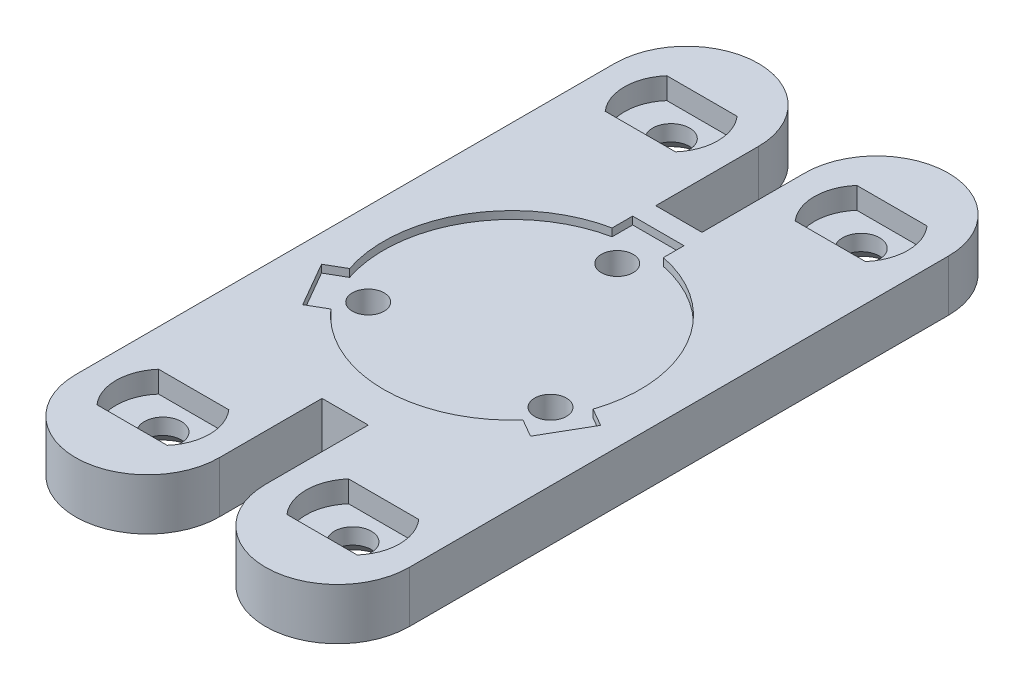
SolidWorks part; units mm, degrees
note: The reader was unsure of these and kept them because the rebuilt part matched: shared geometry of "Sketch6<4>".
ref_plane "Front Plane" through (0, 0, 0) normal (0, 0, 1) x (1, 0, 0)
ref_plane "Top Plane" through (0, 0, 0) normal (0, 1, 0) x (1, 0, 0)
ref_plane "Right Plane" through (0, 0, 0) normal (1, 0, 0) x (0, 0, -1)
sketch "Sketch1" plane through (0, 0, 0) normal (0, 1, 0) x (1, 0, 0)
  line L0 (-16.25, 16.25) -> (-16.25, 26.25)
  line L1 (-16.25, 16.25) -> (16.25, 16.25)
  line L2 (-16.25, 16.25) -> (-16.25, -16.25)
  line L4 (16.25, 16.25) -> (16.25, -16.25)
  line L5 (-16.25, 16.25) -> (16.25, -16.25) construction
  line L6 (-16.25, -16.25) -> (16.25, 16.25) construction
  line L7 (-2.25, 26.25) -> (-2.25, 16.25)
  line L8 (0, 0) -> (0, 7.4679) construction
  line L9 (-16.25, -16.25) -> (16.25, -16.25)
  arc A0 (-16.25, 26.25) -> (-2.25, 26.25) centre (-9.25, 26.25) cw
  point P10 (0, 0)
  dimension "D2" = 14
  dimension "D1" = 32.5
  dimension "D4" = 10
extrude "Boss-Extrude1" add sketch "Sketch1" along normal blind 5
sketch "Sketch2" plane through (0, 0, 0) normal (0, -1, 0) x (1, 0, 0)
  line L11 (-9.25, -16.25) -> (-9.25, -33.25) construction
  line L12 (-16.25, -16.25) -> (-2.25, -16.25) construction
  line L13 (-16.25, 16.25) -> (-16.25, -26.25) construction
  arc A2 (-16.25, -26.25) -> (-2.25, -26.25) centre (-9.25, -26.25) ccw construction
  point P69 (-9.25, -24.75)
hole_wizard "CSK for M3 Flat Head Machine Screw1" positions "Sketch2" profile "Sketch3" countersink size "M3" standard "ANSI Metric" end condition through all
sketch "Sketch3" plane through (-9.25, 0, -24.75) normal (1, 0, 0) x (0, 0, -1)
  line L0 (0, 0) -> (0, 5)
  line L1 (0, 5) -> (1.8, 5)
  line L2 (1.8, 5) -> (1.8, 1.35)
  line L3 (1.8, 1.35) -> (3.15, 0)
  line L5 (3.15, 0) -> (0, 0)
  line L6 (-1.8, 1.35) -> (-3.15, 0) construction
  line L11 (0, -6.35) -> (0, 107.95) construction
  dimension "Thru Hole Dia." = 3.6
  dimension "Thru Hole Depth" = 5
  dimension "Near C'Sink Dia." = 6.3
  dimension "Near C'Sink Angle" = 90
sketch "Sketch16" plane through (0, 5, 0) normal (0, 1, 0) x (1, 0, 0)
  line L0 (-9.25, 24.75) -> (-6.7386, 24.75) construction
  line L1 (-12.6709, 27.75) -> (-5.8291, 27.75)
  line L2 (-12.6709, 21.75) -> (-5.8291, 21.75)
  circle A0 centre (-9.25, 24.75) radius 4.55
  dimension "D1" = 9.1
  dimension "D2" = 6
extrude "Cut-Extrude7" cut sketch "Sketch16" against normal blind 2.1
mirror "Mirror2" about plane through (0, 0, 0) normal (1, 0, 0) of "Boss-Extrude1", "CSK for M3 Flat Head Machine Screw1", "Cut-Extrude7"
mirror "Mirror6" about plane through (0, 0, 0) normal (0, 0, 1) of "Mirror2", "Boss-Extrude1", "CSK for M3 Flat Head Machine Screw1", "Cut-Extrude7"
sketch "Sketch6" plane through (0, 5, 0) normal (0, 1, 0) x (1, 0, 0)
  line L1 (-2.5, 14.25) -> (2.5, 14.25)
  line L2 (0, 0) -> (0, 4.4626) construction
  line L3 (-2.5, 14.25) -> (-2.5, 10.75)
  line L4 (-2.5, 10.75) -> (2.5, 10.75)
  line L5 (2.5, 14.25) -> (2.5, 10.75)
  line L6 (-2.5, 14.25) -> (2.5, 10.75) construction
  line L7 (-2.5, 10.75) -> (2.5, 14.25) construction
  circle A0 centre (0, 0) radius 12.5
  circle A1 centre (0, 0) radius 10.25 construction
  point P4 (0, 12.5)
  dimension "D1" = 25
  dimension "D2" = 2.25
  dimension "D3" = 5
  dimension "D4" = 3.5
extrude "Cut-Extrude2" cut sketch "Sketch6" against normal blind 0.75
extrude "Cut-Extrude5" cut sketch "Sketch6<4>" against normal up to surface (0.75 mm away)
sketch "Sketch6<4>" plane through (0, 5, 0) normal (0, 1, 0) x (1, 0, 0) same geometry as "Sketch6"
sketch "Sketch7" plane through (0, 4.25, 0) normal (0, 1, 0) x (1, 0, 0)
  arc A0 (-2.5, 12.2474) -> (2.5, 12.2474) centre (0, 0) ccw construction
  arc A1 (-2.5, 12.2474) -> (2.5, 12.2474) centre (0, 0) ccw construction
  circle A2 centre (0, 0) radius 10.25
  point P4 (0, 10.25)
  dimension "D1" = 20.5
sketch "Sketch11" plane through (0, 0, 0) normal (0, -1, 0) x (1, 0, 0)
  line L0 (0, 0) -> (0, -12.5) construction
  line L29 (2.5, -14.25) -> (2.5, -12.2474)
  line L30 (2.5, -14.25) -> (2.5, -12.2474)
  line L31 (-2.5, -14.25) -> (2.5, -14.25)
  line L32 (-2.5, -14.25) -> (2.5, -14.25)
  line L33 (-2.5, -12.2474) -> (-2.5, -14.25)
  line L34 (-2.5, -12.2474) -> (-2.5, -14.25)
  arc A2 (2.5, -12.2474) -> (-2.5, -12.2474) centre (0, 0) ccw
  circle A4 centre (0, 0) radius 12.5
  point P8 (0, -12.5)
  point P42 (0, 12.5)
  point P55 (0, -12.5)
  point P57 (0, -10.25)
  point P160 (-2.5, -14.25)
  dimension "D1" = 0
hole_wizard "CSK for M2.5 Flat Head Machine Screw3" positions "Sketch11" profile "Sketch14" countersink size "M2.5" standard "ANSI Metric"
sketch "Sketch14" plane through (0, 0, -10.25) normal (1, 0, 0) x (0, 0, -1)
  line L0 (0, 0) -> (0, 5)
  line L1 (0, 5) -> (1.55, 5)
  line L2 (1.55, 5) -> (1.55, 1.2)
  line L3 (1.55, 1.2) -> (2.75, 0)
  line L5 (2.75, 0) -> (0, 0)
  line L6 (-1.55, 1.2) -> (-2.75, 0) construction
  line L11 (0, -6.35) -> (0, 107.95) construction
  dimension "Thru Hole Dia." = 3.1
  dimension "Thru Hole Depth" = 5
  dimension "Near C'Sink Dia." = 5.5
  dimension "Near C'Sink Angle" = 90
pattern_circular "CirPattern1" count 3 over 360 about axis through (0, 0, 0) along (0, 1, 0) of "Cut-Extrude5", "CSK for M2.5 Flat Head Machine Screw3"
sketch "Sketch18" plane through (0, 5, 0) normal (0, 1, 0) x (1, 0, 0)
  line L1 (9.25, -24.75) -> (-9.25, -24.75)
  line L2 (9.25, -24.75) -> (9.25, 24.75)
  line L3 (9.25, 24.75) -> (-9.25, 24.75)
  line L4 (-9.25, -24.75) -> (-9.25, 24.75)
  dimension "D1" = 49.5
  dimension "D2" = 18.5
equation "\"D2@Sketch6\"=1+1.25"
